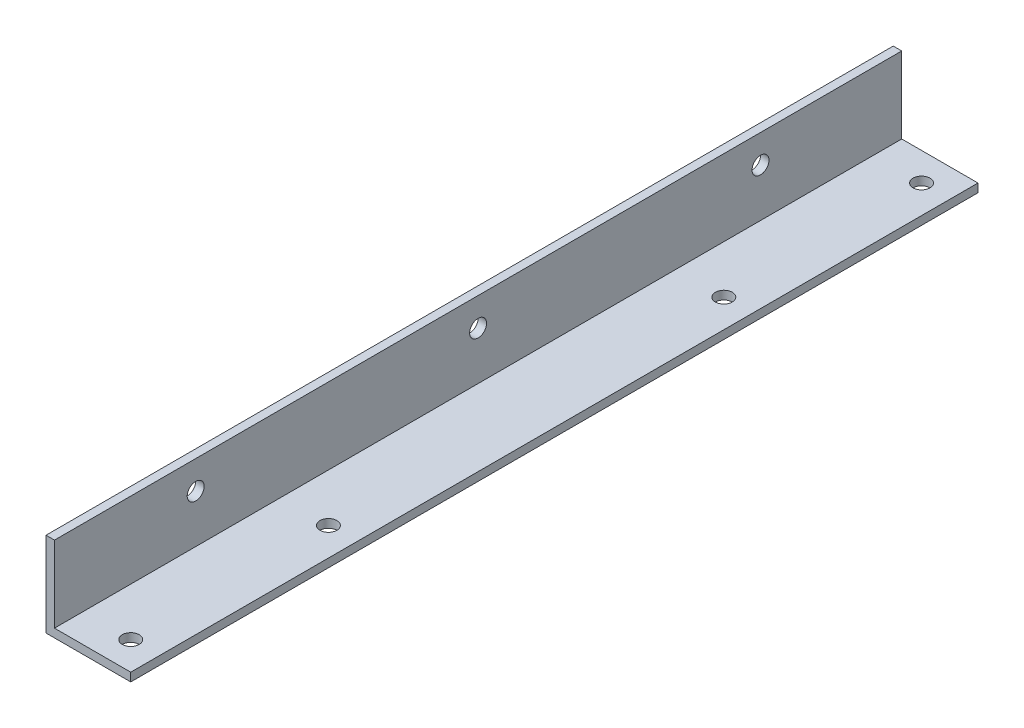
SolidWorks part; units mm, degrees
ref_plane "Plan de face" through (0, 0, 0) normal (0, 0, 1) x (1, 0, 0)
ref_plane "Plan de dessus" through (0, 0, 0) normal (0, 1, 0) x (1, 0, 0)
ref_plane "Plan de droite" through (0, 0, 0) normal (1, 0, 0) x (0, 0, -1)
sketch "Esquisse1" plane through (0, 0, 0) normal (0, 0, 1) x (1, 0, 0)
  line L1 (0, 0) -> (2, 0)
  line L2 (0, 0) -> (0, 15)
  line L3 (0, 15) -> (1.5, 15)
  line L4 (1.5, 1.5) -> (1.5, 15)
  line L5 (2, 0) -> (15, 0)
  line L7 (1.5, 1.5) -> (15, 1.5)
  line L8 (15, 0) -> (15, 1.5)
  dimension "D1" = 15
  dimension "D2" = 1.5
  dimension "D3" = 1.5
  dimension "D4" = 13.5
extrude "Extrusion1" add sketch "Esquisse1" along normal blind 75 and the other way blind 75
sketch "Esquisse2" plane through (1.5, 0, 0) normal (1, 0, 0) x (0, 0, -1)
  line L0 (-75, 1.5) -> (-75, 15) construction
  line L1 (75, 15) -> (-75, 15) construction
  circle A0 centre (-50, 10) radius 1.5
  dimension "D3" = 3
  dimension "D1" = 25
  dimension "D2" = 5
extrude "Extrusion2" cut sketch "Esquisse2" against normal through all
sketch "Esquisse3" plane through (0, 0, 0) normal (0, -1, 0) x (1, 0, 0)
  line L0 (0, 75) -> (15, 75) construction
  line L1 (15, -75) -> (15, 75) construction
  circle A0 centre (10, 70) radius 1.5
  point P2 (7.5, 75)
  dimension "D1" = 3
  dimension "D2" = 5
  dimension "D3" = 5
extrude "Extrusion3" cut sketch "Esquisse3" against normal through all
pattern_linear "Répétition linéaire1" count 3 spacing 50 along (0, 0, -1) of "Extrusion2"
pattern_linear "Répétition linéaire2" count 5 spacing 35 along (0, 0, -1) skipping (2, 0) of "Extrusion3"
